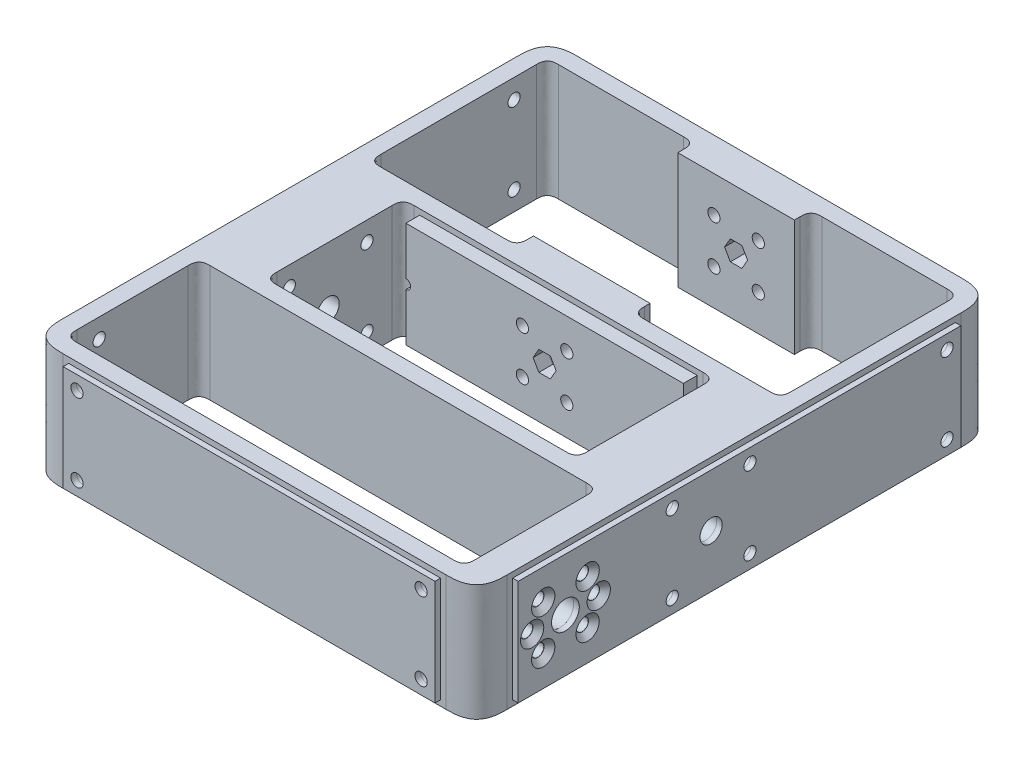
SolidWorks part; units mm, degrees
ref_plane "Front Plane" through (0, 0, 0) normal (0, 0, 1) x (1, 0, 0)
ref_plane "Top Plane" through (0, 0, 0) normal (0, 1, 0) x (1, 0, 0)
ref_plane "Right Plane" through (0, 0, 0) normal (1, 0, 0) x (0, 0, -1)
sketch "Sketch1" plane through (0, 0, 0) normal (0, 1, 0) x (1, 0, 0)
  line L0 (-93.2979, 0) -> (107.2162, 0) construction
  line L1 (-93.2979, -52.5) -> (97.3404, -52.5) construction
  line L2 (-74, -76.5) -> (74, -76.5)
  line L3 (-80, 103) -> (80, 103)
  line L4 (-80, 103) -> (-80, -82.5)
  line L5 (-80, -82.5) -> (80, -82.5)
  line L6 (80, 103) -> (80, -82.5)
  line L7 (74, -76.5) -> (74, -28.5)
  line L8 (74, -28.5) -> (-74, -28.5)
  line L9 (-74, -28.5) -> (-74, -76.5)
  line L10 (-74, 97) -> (-74, 33)
  line L11 (-56, 27) -> (56, 27)
  line L12 (-56, 27) -> (-56, -22.5)
  line L13 (-56, -22.5) -> (56, -22.5)
  line L14 (56, 27) -> (56, -22.5)
  line L15 (-74, 33) -> (-21, 33)
  line L16 (-21, 33) -> (-21, 39)
  line L17 (-21, 39) -> (21, 39)
  line L18 (21, 39) -> (21, 33)
  line L19 (21, 33) -> (74, 33)
  line L20 (74, 33) -> (74, 97)
  line L22 (-74, 97) -> (-21, 97)
  line L23 (-21, 97) -> (-21, 91)
  line L24 (-21, 91) -> (21, 91)
  line L25 (21, 91) -> (21, 97)
  line L26 (21, 97) -> (74, 97)
  line L27 (-117.8349, 65) -> (117.8349, 65) construction
  line L28 (0, 91) -> (0, 39) construction
  point P9 (0, -82.5)
  point P29 (0, -22.5)
  point P31 (0, 91)
  point P36 (0, 65)
  dimension "D1" = 52.5
  dimension "D3" = 160
  dimension "D2" = 6
  dimension "D5" = 6
  dimension "D6" = 24
  dimension "D7" = 24
  dimension "D8" = 6
  dimension "D9" = 24
  dimension "D10" = 6
  dimension "D11" = 6
  dimension "D12" = 6
  dimension "D13" = 42
  dimension "D14" = 12
  dimension "D4" = 65
  dimension "D15" = 52
extrude "Boss-Extrude2" add sketch "Sketch1" along normal mid plane 42
fillet "Fillet2" radius 11 4 edges at (80, 0, -103) (-80, 0, 82.5) (-80, 0, -103) (80, 0, 82.5) curvature continuous yes
sketch "Sketch11" plane through (0, 0, 0) normal (0, 1, 0) x (1, 0, 0)
  line L8 (74, -28.5) -> (-74, -28.5) construction
  line L9 (69.5, -28.5) -> (80, -28.5)
  line L10 (82, 35.9489) -> (82, -108.345) construction
  line L11 (80, -71.5) -> (80, 92) construction
  line L12 (69.5, -28.5) -> (69.5, -76.5)
  line L13 (69.5, -76.5) -> (79.5287, -76.5)
  line L14 (80, -28.5) -> (80, -71.5)
  line L15 (-74, -76.5) -> (74, -76.5) construction
  line L16 (79.5287, -76.5) -> (80, -76.5) construction
  line L17 (80, -71.5) -> (80, -76.5) construction
  spline S0 degree 2 poles (-928.7412, -15.3439) (41.6602, -84.362) (71.2832, -82.4484) (72.514, -82.3689) (73.5428, -82.1401) (76.0869, -81.5744) (77.5752, -80.092) (79.066, -78.6071) (79.6366, -76.0586) (79.8669, -75.03) (79.9474, -73.7973) (81.8879, -44.1188) (12.1756, 926.183) knots -4.508241 -4.508241 -4.508241 0.125 0.125 0.25 0.25 0.5 0.5 0.75 0.75 0.875 0.875 5.490692 5.490692 5.490692 only from (69, -82.5) to (80, -71.5) construction
  spline S1 degree 2 poles (79.5287, -76.5) (79.5862, -76.2834) (79.6366, -76.0586) (79.8669, -75.03) (79.9474, -73.7973) (80, -72.9936) (80, -71.5) knots 0.727944 0.727944 0.727944 0.75 0.75 0.875 0.875 1 1 1
  spline S2 degree 2 poles (69, -82.5) (70.484, -82.5) (71.2832, -82.4484) (72.514, -82.3689) (73.5428, -82.1401) (76.0869, -81.5744) (77.5752, -80.092) (78.9345, -78.7381) (79.5287, -76.5) knots 0 0 0 0.125 0.125 0.25 0.25 0.5 0.5 0.727944 0.727944 0.727944 construction
  dimension "D1" = 2
  dimension "D2" = 12.5
extrude "Boss-Extrude5" add sketch "Sketch11" along normal mid plane 42
sketch "Sketch5" plane through (80, 0, 0) normal (1, 0, 0) x (0, 0, -1)
  line L8 (90, 19) -> (-69.5, 19)
  line L9 (-69.5, 19) -> (-69.5, -19)
  line L10 (-69.5, -19) -> (90, -19)
  line L11 (90, -19) -> (90, 19)
  line L12 (90, 19) -> (-69.5, 19)
  line L14 (-69.5, -19) -> (90, -19)
  line L15 (90, -19) -> (90, 19)
  line L19 (-69.5, 19) -> (-69.5, -19)
  dimension "D1" = 2
extrude "Boss-Extrude3" add sketch "Sketch5" along normal blind 2 separate body
sketch "Sketch9" plane through (-80, 0, 0) normal (-1, 0, 0) x (0, 0, 1)
  line L8 (-90, -19) -> (69.5, -19)
  line L9 (69.5, -19) -> (69.5, 19)
  line L10 (69.5, 19) -> (-90, 19)
  line L11 (-90, 19) -> (-90, -19)
  line L12 (-90, -19) -> (69.5, -19)
  line L13 (69.5, -19) -> (69.5, 19)
  line L14 (69.5, 19) -> (-90, 19)
  line L15 (-90, 19) -> (-90, -19)
  dimension "D1" = 2
extrude "Boss-Extrude4" add sketch "Sketch9" along normal blind 2 separate body
sketch "Sketch8" plane through (82, 0, 0) normal (1, 0, 0) x (0, 0, -1)
  line L1 (-14, 14) -> (14, 14) construction
  line L2 (-14, 14) -> (-14, -14) construction
  line L3 (-14, -14) -> (14, -14) construction
  line L4 (14, 14) -> (14, -14) construction
  line L5 (-14, 14) -> (14, -14) construction
  line L6 (-14, -14) -> (14, 14) construction
  line L16 (85, -14) -> (85, 14)
  line L17 (85, 14) -> (-64.5, 14)
  line L18 (-64.5, 14) -> (-64.5, -14)
  line L19 (-64.5, -14) -> (85, -14)
  line L20 (85, -14) -> (85, 14) construction
  line L21 (85, 14) -> (-64.5, 14) construction
  line L22 (-64.5, 14) -> (-64.5, -14) construction
  line L23 (-64.5, -14) -> (85, -14) construction
  circle A0 centre (0, 0) radius 4
  circle A1 centre (-14, 14) radius 2.2
  circle A2 centre (14, 14) radius 2.2
  circle A3 centre (14, -14) radius 2.2
  circle A4 centre (-14, -14) radius 2.2
  circle A9 centre (85, -14) radius 2.2
  circle A10 centre (85, 14) radius 2.2
  dimension "D1" = 8
  dimension "D2" = 4.4
  dimension "D4" = 5
extrude "Cut-Extrude5" cut sketch "Sketch8" against normal through all
sketch "Sketch6" plane through (0, 0, 0) normal (1, 0, 0) x (0, 0, -1)
  line L0 (-64.5, 0) -> (-40.5, 0) construction
  line L1 (-60.5, 8) -> (-44.5, 8) construction
  line L2 (-60.5, 8) -> (-60.5, -8) construction
  line L3 (-60.5, -8) -> (-44.5, -8) construction
  line L4 (-44.5, 8) -> (-44.5, -8) construction
  line L5 (-60.5, 8) -> (-44.5, -8) construction
  line L6 (-60.5, -8) -> (-44.5, 8) construction
  circle A0 centre (-52.5, 0) radius 5
  circle A1 centre (-60.5, 8) radius 2.2
  circle A2 centre (-44.5, 8) radius 2.2
  circle A3 centre (-44.5, -8) radius 2.2
  circle A4 centre (-60.5, -8) radius 2.2
  circle A5 centre (-64.5, 0) radius 2.2
  circle A6 centre (-40.5, 0) radius 2.2
  dimension "D1" = 52.5
  dimension "D4" = 4.4
  dimension "D5" = 10
  dimension "D2" = 16
  dimension "D3" = 24
extrude "Cut-Extrude3" cut sketch "Sketch6" along normal through all
sketch "Sketch17" plane through (-82, 0, 0) normal (-1, 0, 0) x (0, 0, 1)
  line L8 (-85, 14) -> (-85, -14)
  line L9 (-85, -14) -> (64.5, -14)
  line L10 (64.5, -14) -> (64.5, 14)
  line L11 (64.5, 14) -> (-85, 14)
  line L12 (-85, 14) -> (-85, -14) construction
  line L13 (-85, -14) -> (64.5, -14) construction
  line L14 (64.5, -14) -> (64.5, 14) construction
  line L15 (64.5, 14) -> (-85, 14) construction
  circle A0 centre (64.5, 14) radius 2.2
  circle A1 centre (64.5, -14) radius 2.2
  dimension "D2" = 4.4
extrude "Cut-Extrude11" cut sketch "Sketch17" against normal up to surface (8 mm away) up to face at (-74, 0, 52.5)
fillet "Fillet4" radius 4 16 edges at (69.5, 0, 28.5) (69.5, 0, 76.5) (-56, 0, -27) (-56, 0, 22.5) (56, 0, 22.5) (56, 0, -27) (74, 0, -33) (-74, 0, -33) (-74, 0, 28.5) (74, 0, -97) (-74, 0, -97) (-74, 0, 76.5) (21, 0, -97) (-21, 0, -97) (-21, 0, -33) (21, 0, -33) curvature continuous yes
sketch "Sketch18" plane through (82, 0, 0) normal (1, 0, 0) x (0, 0, -1)
  circle A0 centre (-60.5, -8) radius 2.2 construction
  circle A1 centre (-64.5, 0) radius 2.2 construction
  circle A2 centre (-60.5, 8) radius 2.2 construction
  circle A3 centre (-44.5, 8) radius 2.2 construction
  circle A4 centre (-40.5, 0) radius 2.2 construction
  circle A5 centre (-44.5, -8) radius 2.2 construction
  circle A6 centre (-60.5, -8) radius 2.2
  circle A7 centre (-64.5, 0) radius 2.2
  circle A8 centre (-60.5, 8) radius 2.2
  circle A9 centre (-44.5, 8) radius 2.2
  circle A10 centre (-40.5, 0) radius 2.2
  circle A11 centre (-44.5, -8) radius 2.2
  point P0 (-60.5, -8)
  point P2 (-64.5, 0)
  point P4 (-60.5, 8)
  point P6 (-44.5, 8)
  point P8 (-40.5, 0)
  point P10 (-44.5, -8)
hole_wizard "CSK for M4 Countersunk Flat Head Screw1" positions "Sketch18" profile "Sketch21" countersink size "M4" standard "DIN"
sketch "Sketch21" plane through (82, -8, 60.5) normal (0, 1, 0) x (0, 0, -1)
  line L0 (0, 0) -> (0, 13.8519)
  line L1 (0, 13.8519) -> (2.25, 12.5)
  line L2 (2.25, 12.5) -> (2.25, 1.95)
  line L3 (2.25, 1.95) -> (4.2, 0)
  line L5 (4.2, 0) -> (0, 0)
  line L6 (-2.25, 1.95) -> (-4.2, 0) construction
  line L10 (0, 13.8519) -> (-2.25, 12.5) construction
  line L11 (0, -6.35) -> (0, 107.95) construction
  dimension "Hole Dia." = 4.5
  dimension "Hole Depth" = 12.5
  dimension "Near C'Sink Dia." = 8.4
  dimension "Near C'Sink Angle" = 90
  dimension "Drill Angle" = 118
sketch "Sketch22" plane through (0, 0, -27) normal (0, 0, 1) x (1, 0, 0)
  line L8 (50, 19) -> (-50, 19)
  line L9 (-50, 19) -> (-50, -19)
  line L10 (-50, -19) -> (50, -19)
  line L11 (50, -19) -> (50, 19)
  line L12 (50, 19) -> (-50, 19)
  line L13 (-50, 19) -> (-50, -19)
  line L15 (50, -19) -> (50, 19)
  line L17 (-50, -19) -> (50, -19)
  dimension "D1" = 2
extrude "Boss-Extrude6" add sketch "Sketch22" along normal blind 5 separate body
sketch "Sketch23" plane through (0, 0, -103) normal (0, 0, -1) x (-1, 0, 0)
  line L8 (67, 19) -> (-67, 19)
  line L9 (-67, 19) -> (-67, -19)
  line L10 (-67, -19) -> (67, -19)
  line L11 (67, -19) -> (67, 19)
  line L12 (67, 19) -> (-67, 19)
  line L13 (-67, 19) -> (-67, -19)
  line L14 (-67, -19) -> (67, -19)
  line L15 (67, -19) -> (67, 19)
  dimension "D1" = 2
extrude "Boss-Extrude7" add sketch "Sketch23" along normal blind 2 separate body
sketch "Sketch24" plane through (0, 0, 0) normal (0, 0, 1) x (1, 0, 0)
  line L1 (4.1569, 0) -> (2.0785, 3.6)
  line L2 (2.0785, 3.6) -> (-2.0785, 3.6)
  line L3 (-2.0785, 3.6) -> (-4.1569, 0)
  line L4 (-4.1569, 0) -> (-2.0785, -3.6)
  line L5 (-2.0785, -3.6) -> (2.0785, -3.6)
  line L6 (2.0785, -3.6) -> (4.1569, 0)
  line L7 (-8, -8) -> (8, -8) construction
  line L8 (-8, -8) -> (-8, 8) construction
  line L9 (-8, 8) -> (8, 8) construction
  line L10 (8, -8) -> (8, 8) construction
  line L11 (-8, -8) -> (8, 8) construction
  line L12 (-8, 8) -> (8, -8) construction
  circle A0 centre (0, 0) radius 3.6 construction
  circle A1 centre (-8, 8) radius 2.2
  circle A2 centre (8, 8) radius 2.2
  circle A3 centre (8, -8) radius 2.2
  circle A4 centre (-8, -8) radius 2.2
  dimension "D3" = 4.4
  dimension "D1" = 7.2
  dimension "D2" = 16
extrude "Cut-Extrude12" cut sketch "Sketch24" against normal through all
sketch "Sketch25" plane through (0, 0, -22) normal (0, 0, 1) x (1, 0, 0)
  line L0 (-50, 0) -> (50, 0) construction
  circle A0 centre (-50, 0) radius 1.705
  circle A1 centre (50, 0) radius 1.705
  dimension "D2" = 3.41
  dimension "D1" = 100
extrude "Cut-Extrude13" cut sketch "Sketch25" against normal up to surface (11 mm away) up to face at (-58.75, 0, -33)
sketch "Sketch27" plane through (0, 0, 82.5) normal (0, 0, 1) x (1, 0, 0)
  line L8 (-67, -19) -> (67, -19)
  line L9 (67, -19) -> (67, 19)
  line L10 (67, 19) -> (-67, 19)
  line L11 (-67, 19) -> (-67, -19)
  line L12 (-67, -19) -> (67, -19)
  line L13 (67, -19) -> (67, 19)
  line L14 (67, 19) -> (-67, 19)
  line L15 (-67, 19) -> (-67, -19)
  dimension "D1" = 2
extrude "Boss-Extrude8" add sketch "Sketch27" along normal blind 2 separate body
sketch "Sketch28" plane through (0, 0, 84.5) normal (0, 0, 1) x (1, 0, 0)
  line L8 (-62, 14) -> (-62, -14)
  line L9 (-62, -14) -> (62, -14)
  line L10 (62, -14) -> (62, 14)
  line L11 (62, 14) -> (-62, 14)
  line L12 (-62, 14) -> (-62, -14) construction
  line L13 (-62, -14) -> (62, -14) construction
  line L14 (62, -14) -> (62, 14) construction
  line L15 (62, 14) -> (-62, 14) construction
  circle A0 centre (-62, 14) radius 2.2
  circle A1 centre (-62, -14) radius 2.2
  circle A2 centre (62, -14) radius 2.2
  circle A3 centre (62, 14) radius 2.2
  dimension "D2" = 4.4
extrude "Cut-Extrude14" cut sketch "Sketch28" against normal up to surface (8 mm away) up to face at (-36.125, 0, 76.5)
equation "\"motor_center_distance_to_axle\"= 52.5mm"
equation "\"width\"= 160mm"
equation "\"height\"= 42mm"
equation "\"wall_thickness\"= 6mm"
equation "\"aluminum_thickness\" = 2.0mm"
equation "\"roll_push_plate_hole_distance\"= 100mm"
equation "\"D1@Sketch1\"=\"motor_center_distance_to_axle\""
equation "\"D3@Sketch1\"=\"width\""
equation "\"depth\"= 200mm"
equation "\"D2@Sketch1\"=\"wall_thickness\""
equation "\"D5@Sketch1\"=\"wall_thickness\""
equation "\"D8@Sketch1\"=\"wall_thickness\""
equation "\"D10@Sketch1\"=\"wall_thickness\""
equation "\"D11@Sketch1\"=\"wall_thickness\""
equation "\"D12@Sketch1\"=\"wall_thickness\""
equation "\"D13@Sketch1\"=\"height\""
equation "\"spine_center_distance_to_axle\"= 65mm"
equation "\"D4@Sketch1\"=\"spine_center_distance_to_axle\""
equation "\"spine_depth\" = 42mm"
equation "\"D15@Sketch1\"=\"spine_depth\"+10mm"
equation "\"D1@Boss-Extrude2\"=\"height\""
equation "\"D1@Boss-Extrude3\"=\"aluminum_thickness\""
equation "\"D1@Sketch6\"=\"motor_center_distance_to_axle\""
equation "\"plate_hole_inset\"= 5mm"
equation "\"D1@Boss-Extrude4\"=\"aluminum_thickness\""
equation "\"D4@Sketch8\"=\"plate_hole_inset\""
equation "\"D1@Boss-Extrude5\"=\"height\""
equation "\"D1@Sketch11\"=\"aluminum_thickness\""
equation "\"D1@Sketch17\"=\"plate_hole_inset\""
equation "\"D1@Boss-Extrude7\"=\"aluminum_thickness\""
equation "\"D1@Sketch25\"=\"roll_push_plate_hole_distance\""
equation "\"D1@Boss-Extrude8\"=\"aluminum_thickness\""
equation "\"D1@Sketch28\"=\"plate_hole_inset\""
equation "\"spine_cavity_depth\"= 80mm"
equation "\"fillet_radius\"= 10mm"
